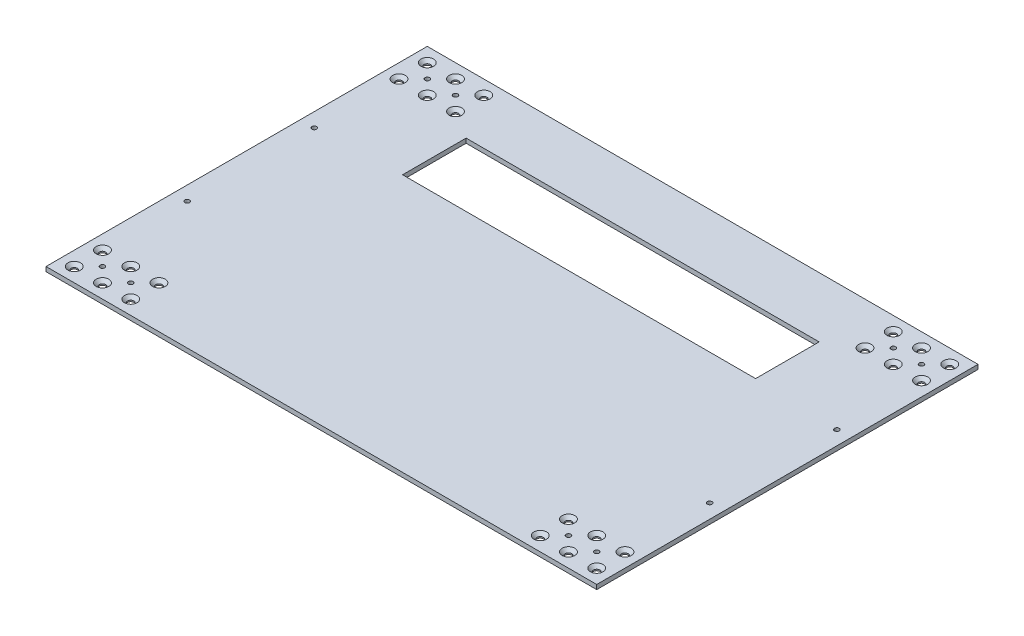
SolidWorks part; units mm, degrees
ref_plane "Front Plane" through (0, 0, 0) normal (0, 0, 1) x (1, 0, 0)
ref_plane "Top Plane" through (0, 0, 0) normal (0, 1, 0) x (1, 0, 0)
ref_plane "Right Plane" through (0, 0, 0) normal (1, 0, 0) x (0, 0, -1)
sketch "Sketch1" plane through (0, 0, 0) normal (0, 1, 0) x (1, 0, 0)
  line L1 (-195, -135) -> (195, -135)
  line L2 (-195, -135) -> (-195, 135)
  line L3 (-195, 135) -> (195, 135)
  line L4 (195, -135) -> (195, 135)
  line L5 (-195, -135) -> (195, 135) construction
  line L6 (-195, 135) -> (195, -135) construction
  point P0 (0, 0)
  dimension "D1" = 390
  dimension "D2" = 270
extrude "Boss-Extrude1" add sketch "Sketch1" along normal blind 3.175
sketch "Sketch2" plane through (0, 3.175, 0) normal (0, 1, 0) x (1, 0, 0)
  line L0 (195, 135) -> (-195, 135) construction
  line L1 (-165.5, 135) -> (165.5, 135)
  line L2 (-165.5, 135) -> (-165.5, -90)
  line L3 (-165.5, -90) -> (165.5, -90)
  line L4 (165.5, 135) -> (165.5, -90)
  line L5 (-165.5, 135) -> (165.5, -90) construction
  line L6 (-165.5, -90) -> (165.5, 135) construction
  line L8 (-125, 47.5) -> (125, 47.5)
  line L9 (-125, 47.5) -> (-125, 92.5)
  line L10 (-125, 92.5) -> (125, 92.5)
  line L11 (125, 47.5) -> (125, 92.5)
  line L12 (-125, 47.5) -> (125, 92.5) construction
  line L13 (-125, 92.5) -> (125, 47.5) construction
  point P0 (0, 22.5)
  point P11 (0, 70)
  dimension "D1" = 331
  dimension "D2" = 225
  dimension "D3" = 45
  dimension "D4" = 250
  dimension "D5" = 65
extrude "Cut-Extrude1" cut sketch "Sketch2" against normal through all contours L9 L8 L11 L10
hole_wizard "CSK for M4 SFHCS2" positions "Sketch3" profile "Sketch4" countersink size "M4" standard "ANSI Metric" end condition through all
sketch "Sketch3" plane through (0, 3.175, 0) normal (0, 1, 0) x (1, 0, 0)
  line L0 (-195, -135) -> (195, -135) construction
  point P0 (-185, -125)
  point P13 (-165, -125)
  point P14 (-145, -125)
  point P15 (-165, -105)
  point P16 (-145, -105)
  point P17 (-185, -105)
  dimension "D1" = 10
  dimension "D2" = 10
  dimension "D3" = 3
  dimension "D4" = 2
sketch "Sketch4" plane through (-185, 3.175, 125) normal (1, 0, 0) x (0, 0, 1)
  line L0 (0, 0) -> (0, 3.175)
  line L1 (0, 3.175) -> (2.25, 3.175)
  line L2 (2.25, 3.175) -> (2.25, 2.23)
  line L3 (2.25, 2.23) -> (4.48, 0)
  line L5 (4.48, 0) -> (0, 0)
  line L6 (-2.25, 2.23) -> (-4.48, 0) construction
  line L11 (0, -6.35) -> (0, 107.95) construction
  dimension "Thru Hole Dia." = 4.5
  dimension "Thru Hole Depth" = 3.175
  dimension "Near C'Sink Dia." = 8.96
  dimension "Near C'Sink Angle" = 90
pattern_linear "LPattern1" count 2 spacing 230 along (0, 0, -1) count 2 spacing 330 along (1, 0, 0) of "CSK for M4 SFHCS2"
hole_wizard "M4x0.7 Tapped Hole1" positions "Sketch5" profile "Sketch6" tap size "M4x0.7" standard "ANSI Metric" end condition through all
sketch "Sketch5" plane through (0, 3.175, 0) normal (0, 1, 0) x (1, 0, 0)
  line L0 (-195, 135) -> (-195, -135) construction
  line L1 (-195, -135) -> (195, -135) construction
  point P17 (-185, -45)
  point P19 (-175, -115)
  point P21 (-155, -115)
  point P29 (0, 0)
  dimension "D2" = 20
  dimension "D1" = 20
  dimension "D3" = 20
  dimension "D4" = 10
  dimension "D5" = 90
sketch "Sketch6" plane through (-185, 3.175, 45) normal (1, 0, 0) x (0, 0, 1)
  line L0 (0, 0) -> (0, 3.175)
  line L1 (0, 3.175) -> (1.65, 3.175)
  line L2 (1.65, 3.175) -> (1.65, 0)
  line L5 (1.65, 0) -> (0, 0)
  line L11 (0, -6.35) -> (0, 107.95) construction
  dimension "Thru Tap Drill Dia." = 3.3
  dimension "Thru Tap Drill Depth" = 3.175
mirror "Mirror1" about plane through (0, 0, 0) normal (1, 0, 0) of "M4x0.7 Tapped Hole1" second plane through (0, 0, 0) second plane normal (0, 0, 1)
